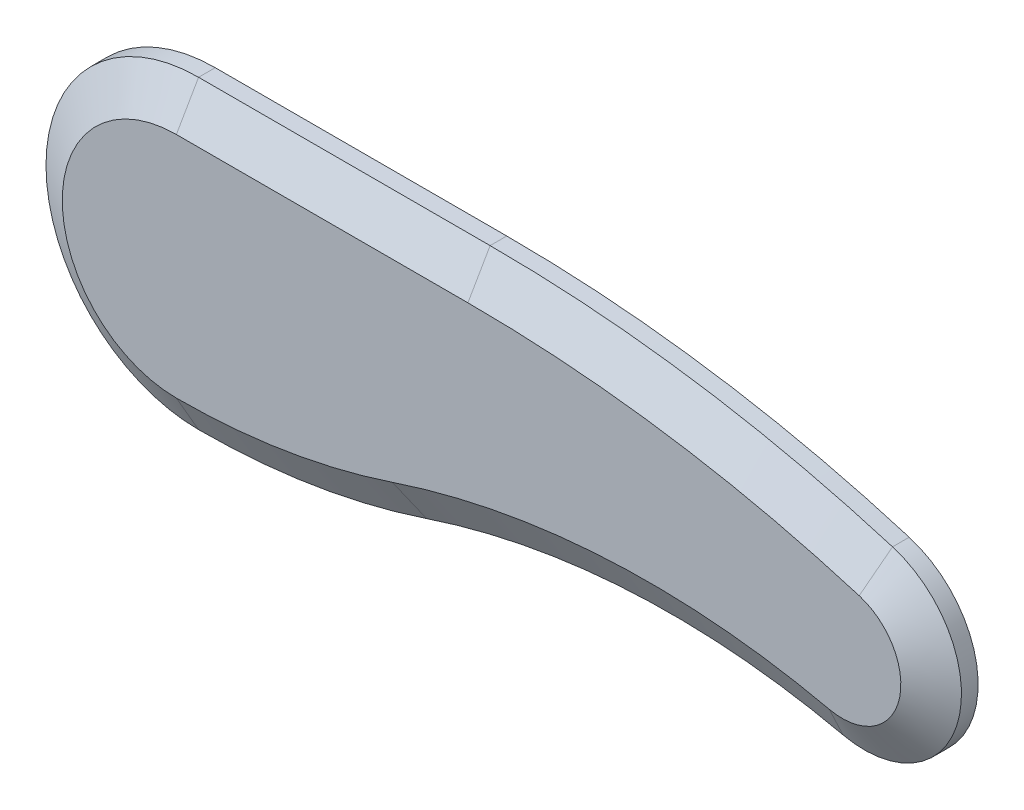
SolidWorks part; units mm, degrees
ref_plane "Front Plane" through (0, 0, 0) normal (0, 0, 1) x (1, 0, 0)
ref_plane "Top Plane" through (0, 0, 0) normal (0, 1, 0) x (1, 0, 0)
ref_plane "Right Plane" through (0, 0, 0) normal (1, 0, 0) x (0, 0, -1)
sketch "Sketch1" plane through (0, 0, 0) normal (0, 0, 1) x (1, 0, 0)
  line L0 (0, 0) -> (120, 0) construction
  line L1 (0, 0) -> (0, -27.5) construction
  line L2 (0, 27.5) -> (52.5463, 27.5)
  circle A0 centre (0, 0) radius 27.5
  circle A2 centre (120, 0) radius 17.5
  arc A3 (52.5463, 27.5) -> (125.0772, 16.7473) centre (52.5463, -222.5) cw
  arc A4 (0, -27.5) -> (41.1063, -20.8299) centre (0, 102.5) ccw
  arc A5 (41.1063, -20.8299) -> (116.1527, -17.0719) centre (85.3746, -153.6468) cw
  dimension "D2" = 55
  dimension "D4" = 35
  dimension "D5" = 250
  dimension "D6" = 140
  dimension "D7" = 130
  dimension "D1" = 120
  dimension "D3" = 0
extrude "Boss-Extrude1" add sketch "Sketch1" along normal blind 7 contours A0 L0 A2 A3 L2 | L0 A0 A4 A5 A2 | A0 | A2 region at (61.3869, 4.6825, 0) region at (0, 0, 0) region at (120, 0, 0)
chamfer "Chamfer1" distance 4 angle 60 6 edges at (20.822, -25.8216, 7) (-27.5, 0, 7) (26.2732, 27.5, 7) (89.2081, 24.7972, 7) (136.9208, -4.4652, 7) (78.3727, -13.822, 7) first distance on face at (20.6876, -24.9933, 3.5) first distance on face at (-13.75, 0, 3.5) first distance on face at (26.2732, 27.5, 3.5) first distance on face at (89.0099, 23.4604, 3.5) first distance on face at (128.7679, -2.3137, 3.5) first distance on face at (78.5011, -16.3864, 3.5)
sketch "Sketch3" plane through (0, 0, 0) normal (0, 0, -1) x (-1, 0, 0)
  circle A0 centre (0, 0) radius 8.5
  circle A1 centre (-120, 0) radius 8.5
  dimension "D1" = 17
  dimension "D2" = 17
extrude "Cut-Extrude2" cut sketch "Sketch3" against normal blind 4
ref_plane "Plane1" through (0, 0, 2.5) normal (0, 0, -1) x (-1, 0, 0)
sketch "Sketch5" plane through (0, 0, 2.5) normal (0, 0, -1) x (-1, 0, 0)
  line L0 (0, 0) -> (-60, 0) construction
  line L1 (0, 0) -> (-83.9535, 13.2969) construction
  line L2 (0, 0) -> (-30.0702, -10.9446) construction
  line L3 (-86.0464, 16.9219) -> (-73.7677, 16.9219)
  line L4 (-81.8606, 9.6719) -> (-79.7677, 13.2969)
  line L5 (-79.7677, 13.2969) -> (-81.8606, 16.9219)
  line L6 (-81.8606, 16.9219) -> (-86.0464, 16.9219)
  line L7 (-86.0464, 16.9219) -> (-88.1393, 13.2969)
  line L8 (-88.1393, 13.2969) -> (-86.0464, 9.6719)
  line L9 (-86.0464, 9.6719) -> (-81.8606, 9.6719)
  line L10 (-57.9071, -3.625) -> (-55.8142, 0)
  line L11 (-55.8142, 0) -> (-57.9071, 3.625)
  line L12 (-57.9071, 3.625) -> (-62.0929, 3.625)
  line L13 (-62.0929, 3.625) -> (-64.1858, 0)
  line L14 (-64.1858, 0) -> (-62.0929, -3.625)
  line L15 (-62.0929, -3.625) -> (-57.9071, -3.625)
  line L16 (-27.9773, -14.5696) -> (-25.8844, -10.9446)
  line L17 (-25.8844, -10.9446) -> (-27.9773, -7.3196)
  line L18 (-27.9773, -7.3196) -> (-32.1631, -7.3196)
  line L19 (-32.1631, -7.3196) -> (-34.256, -10.9446)
  line L20 (-34.256, -10.9446) -> (-32.1631, -14.5696)
  line L21 (-32.1631, -14.5696) -> (-27.9773, -14.5696)
  line L22 (-86.0464, 9.6719) -> (-73.7677, 9.6719)
  line L23 (-73.7677, 16.9219) -> (-73.7677, 9.6719) construction
  line L24 (-62.0929, 3.625) -> (-49.8142, 3.625)
  line L25 (-62.0929, -3.625) -> (-49.8142, -3.625)
  line L26 (-49.8142, 3.625) -> (-49.8142, -3.625) construction
  line L27 (-32.1631, -7.3196) -> (-19.8844, -7.3196)
  line L28 (-32.1631, -14.5696) -> (-19.8844, -14.5696)
  line L29 (-19.8844, -14.5696) -> (-19.8844, -7.3196) construction
  circle A0 centre (-83.9535, 13.2969) radius 3.625 construction
  circle A1 centre (-60, 0) radius 3.625 construction
  circle A2 centre (-30.0702, -10.9446) radius 3.625 construction
  circle A3 centre (-73.7677, 13.2969) radius 6
  circle A4 centre (-49.8142, 0) radius 6
  circle A5 centre (-19.8844, -10.9446) radius 6
  circle A6 centre (-83.9535, 13.2969) radius 2.125
  circle A7 centre (-60, 0) radius 2.125
  circle A8 centre (-30.0702, -10.9446) radius 2.125
  dimension "D7" = 12
  dimension "D8" = 4.25
  dimension "D1" = 20
  dimension "D2" = 9
  dimension "D3" = 85
  dimension "D4" = 60
  dimension "D5" = 32
  dimension "D6" = 7.25
extrude "Cut-Extrude3" cut sketch "Sketch5" against normal blind 3.5 contours L8 L9 L4 L5 L3 L7 | A3 | A3 L3 L5 | A3 L4 L22 | L14 L15 L10 L11 L12 L13 | A4 L24 L11 | A4 L10 L25 | A4 | A5 | A5 L16 L28 | A5 L27 L17 | L20 L21 L16 L17 L18 L19 | A7 | A8 | A6 region at (83.9535, 16.8112, 2.5) region at (80.1796, 15.8006, 2.5) region at (73.7677, 13.2969, 2.5) region at (80.1796, 10.7933, 2.5) region at (60, -3.5143, 2.5) region at (56.2261, -2.5037, 2.5) region at (56.2261, 2.5037, 2.5) region at (49.8142, 0, 2.5) region at (30.0702, -14.4589, 2.5) region at (26.2963, -13.4483, 2.5) region at (26.2963, -8.441, 2.5) region at (19.8844, -10.9446, 2.5) region at (60, 0, 2.5) region at (30.0702, -10.9446, 2.5)
extrude "Cut-Extrude4" cut sketch "Sketch5<3>" along normal through all contours A3 | A4 | A5 | A6 | A7 | A8 region at (73.7677, 13.2969, 2.5) region at (49.8142, 0, 2.5) region at (19.8844, -10.9446, 2.5) region at (83.9535, 13.2969, 2.5) region at (60, 0, 2.5) region at (30.0702, -10.9446, 2.5)
sketch "Sketch5<3>" plane through (0, 0, 2.5) normal (0, 0, -1) x (-1, 0, 0) same geometry as "Sketch5"
chamfer "Chamfer2" distance 0.5 angle 70 3 edges at (67.7677, 13.2969, 6) (13.8844, -10.9446, 6) (43.8142, 0, 6) first distance on face at (76.1583, 13.2969, 4.25) first distance on face at (22.2749, -10.9446, 4.25) first distance on face at (52.2048, 0, 4.25)
sketch "Sketch7" plane through (0, 0, 0) normal (0, 0, -1) x (-1, 0, 0)
  circle A0 centre (0, 0) radius 9.5
  circle A1 centre (0, 0) radius 8.5 construction
  circle A2 centre (0, 0) radius 8.5
  circle A3 centre (-120, 0) radius 8.5 construction
  circle A4 centre (-120, 0) radius 8.5
  circle A5 centre (-120, 0) radius 9.5
  dimension "D1" = 1
  dimension "D2" = 1
extrude "Boss-Extrude2" add sketch "Sketch7" along normal blind 0.5
